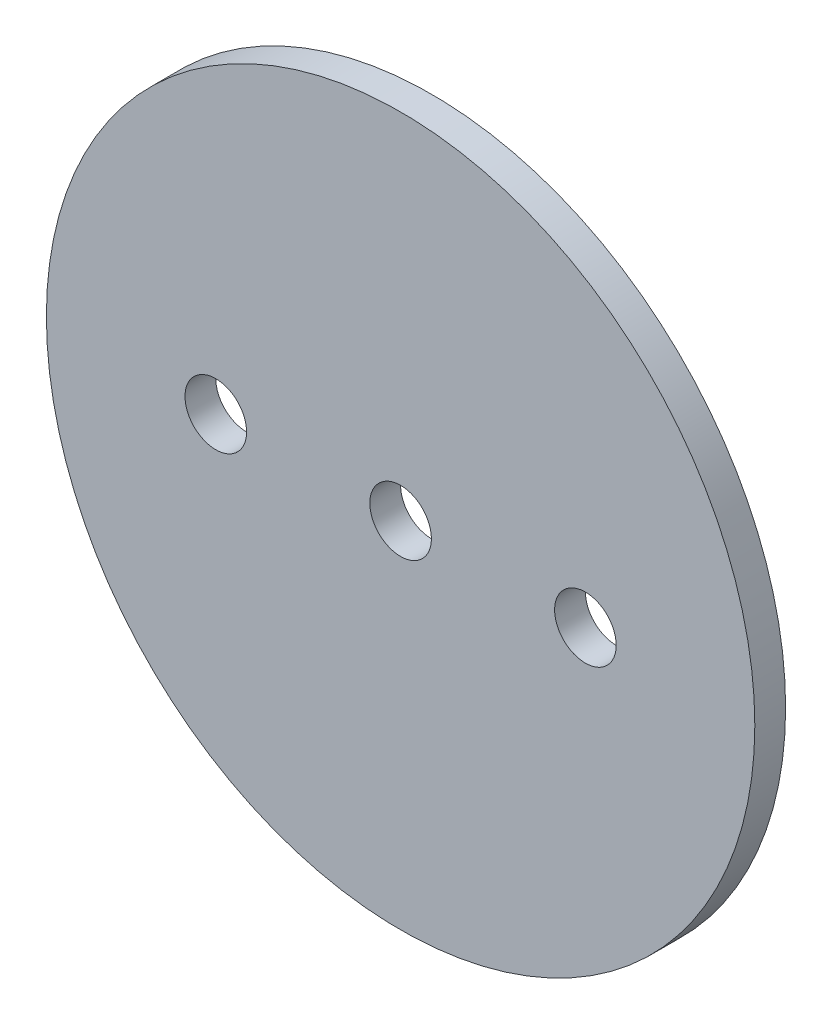
SolidWorks part; units mm, degrees
ref_plane "Front Plane" through (0, 0, 0) normal (0, 0, 1) x (1, 0, 0)
ref_plane "Top Plane" through (0, 0, 0) normal (0, 1, 0) x (1, 0, 0)
ref_plane "Right Plane" through (0, 0, 0) normal (1, 0, 0) x (0, 0, -1)
sketch "Sketch1" plane through (0, 0, 0) normal (0, 0, 1) x (1, 0, 0)
  circle A0 centre (0, 0) radius 36.5125
  dimension "D1" = 73.025
extrude "Boss-Extrude1" add sketch "Sketch1" along normal mid plane 3.175
sketch "Sketch2" plane through (0, 0, 1.5875) normal (0, 0, 1) x (1, 0, 0)
  line L0 (-1000, 0) -> (49000, 0) construction
  point P1 (0, 0)
  point P4 (19.05, 0)
  point P5 (-19.05, 0)
  dimension "D1" = 19.05
  dimension "D2" = 38.1
hole_wizard "1/4 (0.25) Diameter Hole1" positions "Sketch2" profile "Sketch3" hole size "1/4" standard "ANSI Inch" end condition through all
sketch "Sketch3" plane through (-19.05, 0, 1.5875) normal (1, 0, 0) x (0, -1, 0)
  line L0 (0, 0) -> (0, 3.175)
  line L1 (0, 3.175) -> (3.175, 3.175)
  line L2 (3.175, 3.175) -> (3.175, 0)
  line L5 (3.175, 0) -> (0, 0)
  line L11 (0, -6.35) -> (0, 107.95) construction
  dimension "Thru Hole Dia." = 6.35
  dimension "Thru Hole Depth" = 3.175
equation "\"AIRFRAME_OD\"= 3.091in"
equation "\"AIRFRAME_ID\"= 3.00in"
equation "\"FLAT_T\" = 0.125in"
equation "\"NOSE_EXP_L\"= 3.5in"
equation "\"NOSE_SHOULDER_L\" = 5in"
equation "\"MAIN_L\" = 30in"
equation "\"RECO_COUP_L\" = 6in"
equation "\"RECO_SWITCH_L\" = 1.5in"
equation "\"DROGUE_L\" = 14in"
equation "\"ATS_FORE_COUP_L\" = 4in"
equation "\"ATS_AFT_COUP_L\" = 4in"
equation "\"LOWER_L\" = 16in"
equation "\"FIN_N\" = 4"
equation "\"CR_AFT_X\" = 0.5in"
equation "\"CR_FORE_X\" = 6in"
equation "\"FIN_ROOT\" = 5in"
equation "\"FIN_X\" = 0.75in"
equation "\"MOTOR_OD\" = 2.25in"
equation "\"MOTOR_ID\" = 2.126in"
equation "\"COUPLER_OD\" = 2.998in"
equation "\"COUPLER_ID\" = 2.875in"
equation "\"D1@Sketch1\"=\"COUPLER_ID\""
equation "\"D1@Boss-Extrude1\"=\"FLAT_T\""
equation "\"RECO_ROD_X\" = 1.5in"
equation "\"ATS_ROD_X\" = 2in"
equation "\"D1@Sketch2\"=\"RECO_ROD_X\"*0.5"
equation "\"D2@Sketch2\"=\"RECO_ROD_X\""
